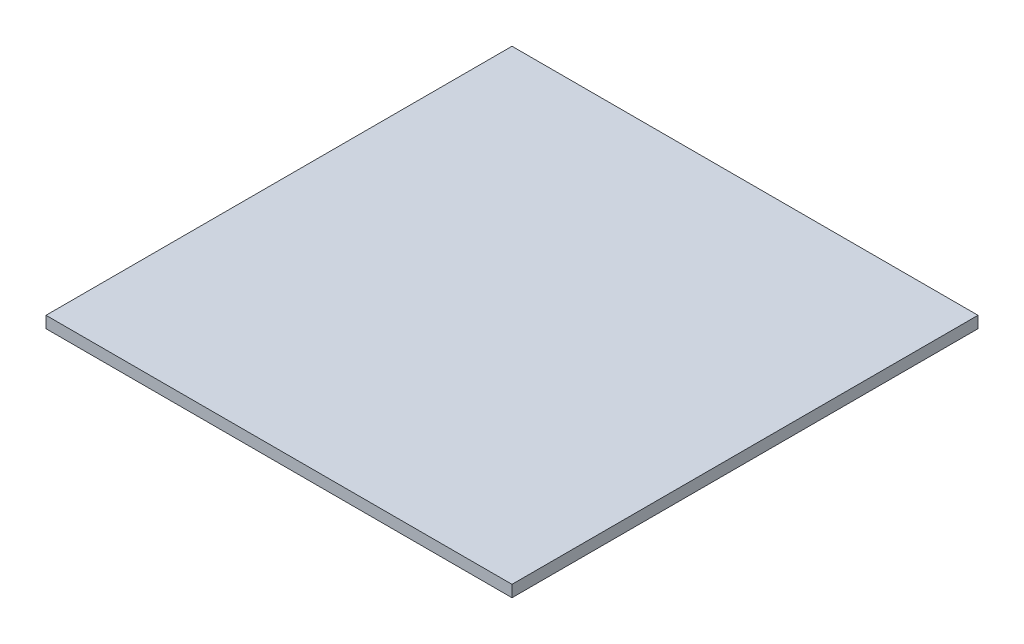
SolidWorks part; units mm, degrees
ref_plane "Front Plane" through (0, 0, 0) normal (0, 0, 1) x (1, 0, 0)
ref_plane "Top Plane" through (0, 0, 0) normal (0, 1, 0) x (1, 0, 0)
ref_plane "Right Plane" through (0, 0, 0) normal (1, 0, 0) x (0, 0, -1)
sketch "Sketch1" plane through (0, 0, 0) normal (0, 1, 0) x (1, 0, 0)
  line L1 (-100, 100) -> (100, 100)
  line L2 (-100, 100) -> (-100, -100)
  line L3 (-100, -100) -> (100, -100)
  line L4 (100, 100) -> (100, -100)
  line L5 (-100, 100) -> (100, -100) construction
  line L6 (-100, -100) -> (100, 100) construction
  point P0 (0, 0)
  dimension "D1" = 200
  dimension "D2" = 200
extrude "Base" add sketch "Sketch1" along normal blind 2.5 and the other way blind 2.5
sketch "Sketch2" plane through (0, -2.5, 0) normal (0, -1, 0) x (-1, 0, 0)
  line L0 (45, -47.5) -> (-45, -47.5)
  line L1 (42.5, -37.5) -> (-42.5, -37.5)
  line L2 (42.5, -37.5) -> (42.5, 37.5)
  line L3 (42.5, 37.5) -> (-42.5, 37.5)
  line L4 (-42.5, -37.5) -> (-42.5, 37.5)
  line L5 (-113.4478, 0) -> (141.2128, 0) construction
  line L6 (0, -175.8738) -> (0, 153.5398) construction
  line L7 (-45, -47.5) -> (-45, 47.5)
  line L8 (45, 47.5) -> (-45, 47.5)
  line L9 (45, -47.5) -> (45, 47.5)
  point P0 (0, 0)
  dimension "D1" = 75
  dimension "D2" = 85
  dimension "D3" = 2.5
  dimension "D4" = 2.5
  dimension "D5" = 10
  dimension "D6" = 10
  dimension "D7" = 0
extrude "BatteryHolder" add sketch "Sketch2" along normal blind 25
